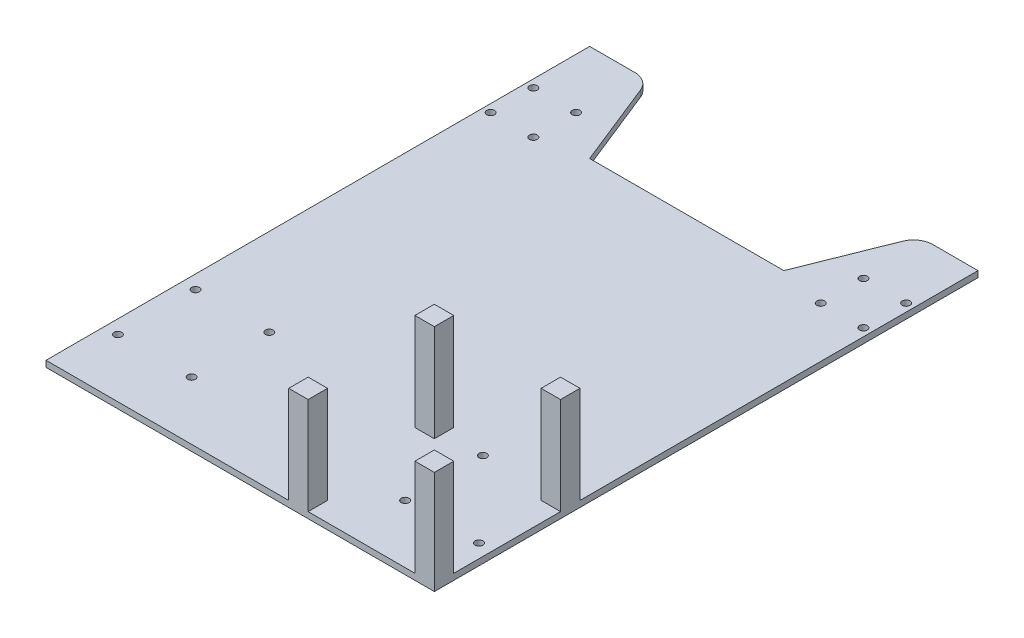
SolidWorks part; units mm, degrees
material "Pine"
ref_plane "Front Plane" through (0, 0, 0) normal (0, 0, 1) x (1, 0, 0)
ref_plane "Top Plane" through (0, 0, 0) normal (0, 1, 0) x (1, 0, 0)
ref_plane "Right Plane" through (0, 0, 0) normal (1, 0, 0) x (0, 0, -1)
sketch "Sketch3" plane through (0, 0, 0) normal (0, 1, 0) x (1, 0, 0)
  line L1 (-100, -140) -> (100, -140)
  line L2 (-100, -140) -> (-100, 140)
  line L3 (-100, 140) -> (100, 140)
  line L4 (100, -140) -> (100, 140)
  line L5 (-100, -140) -> (100, 140) construction
  line L6 (-100, 140) -> (100, -140) construction
  point P0 (0, 0)
  dimension "D1" = 200
  dimension "D2" = 280
extrude "Boss-Extrude1" add sketch "Sketch3" along normal blind 3.175
sketch "Sketch4" plane through (0, 3.175, 0) normal (0, 1, 0) x (1, 0, 0)
  line L0 (100, -140) -> (100, 140) construction
  line L1 (100, -140) -> (90, -140)
  line L2 (100, -140) -> (100, -130)
  line L3 (100, -65) -> (90, -65)
  line L4 (25, -140) -> (25, -130)
  line L5 (-100, -140) -> (100, -140) construction
  line L6 (35, -140) -> (35, -130)
  line L7 (90, -65) -> (90, -75)
  line L8 (35, -65) -> (25, -65)
  line L9 (35, -140) -> (25, -140)
  line L10 (25, -130) -> (35, -130)
  line L11 (25, -75) -> (35, -75)
  line L12 (90, -75) -> (100, -75)
  line L13 (90, -130) -> (100, -130)
  line L14 (25, -75) -> (25, -65)
  line L15 (35, -75) -> (35, -65)
  line L16 (90, -130) -> (90, -140)
  line L17 (100, -75) -> (100, -65)
  point P20 (95, -130)
  dimension "D1" = 0
  dimension "D2" = 0
  dimension "D3" = 75
  dimension "D4" = 75
  dimension "D5" = 10
  dimension "D6" = 10
  dimension "D7" = 10
  dimension "D8" = 10
  dimension "D9" = 10
extrude "Boss-Extrude2" add sketch "Sketch4" along normal blind 50
sketch "Sketch7" plane through (0, 0, 0) normal (0, -1, 0) x (1, 0, 0)
  line L0 (100, 140) -> (100, -140) construction
  line L1 (-100, 140) -> (100, 140) construction
  line L2 (100, -140) -> (-100, -140) construction
  line L3 (0, 0) -> (0, -140) construction
  line L4 (-93, 70) -> (93, 70) construction
  line L5 (-93, 110) -> (93, 110) construction
  line L6 (-100, -140) -> (-100, 140) construction
  circle A8 centre (-93, 70) radius 2
  circle A9 centre (-93, 110) radius 2
  circle A10 centre (-55, 110) radius 2
  circle A11 centre (-55, 70) radius 2
  circle A12 centre (55, 110) radius 2
  circle A13 centre (93, 110) radius 2
  circle A14 centre (93, 70) radius 2
  circle A15 centre (55, 70) radius 2
  circle A16 centre (96, -107) radius 2
  circle A17 centre (74, -85) radius 2
  circle A18 centre (96, -85) radius 2
  circle A19 centre (74, -107) radius 2
  circle A20 centre (-74, -107) radius 2
  circle A21 centre (-96, -107) radius 2
  circle A22 centre (-96, -85) radius 2
  circle A23 centre (-74, -85) radius 2
  dimension "D17" = 40
  dimension "D4" = 7
  dimension "D1" = 38
  dimension "D2" = 40
  dimension "D3" = 38
  dimension "D5" = 38
  dimension "D6" = 40
  dimension "D7" = 38
  dimension "D8" = 4
  dimension "D9" = 33
  dimension "D10" = 22
  dimension "D11" = 22
  dimension "D16" = 7
  dimension "D18" = 55.1725
  dimension "D19" = 40
  dimension "D20" = 55.1725
  dimension "D27" = 30
extrude "Cut-Extrude2" cut sketch "Sketch7" against normal blind 10
sketch "Sketch8" plane through (0, 3.175, 0) normal (0, 1, 0) x (1, 0, 0)
  line L0 (-100, -140) -> (25, -140) construction
  line L1 (-100, 140) -> (-100, -140) construction
  line L2 (100, -65) -> (100, 140) construction
  circle A0 centre (-35, -35) radius 4
  circle A1 centre (-15, -35) radius 4
  circle A5 centre (-35, 40) radius 4
  circle A6 centre (-15, 40) radius 4
  circle A7 centre (45, 2.5) radius 4
  circle A8 centre (65, 2.5) radius 4
  dimension "D1" = 8
  dimension "D2" = 8
  dimension "D4" = 8
  dimension "D5" = 8
  dimension "D7" = 8
  dimension "D8" = 8
  dimension "D3" = 20
  dimension "D6" = 20
  dimension "D9" = 20
  dimension "D10" = 105
  dimension "D11" = 65
  dimension "D12" = 65
  dimension "D13" = 75
  dimension "D14" = 37.5
  dimension "D15" = 35
extrude "Cut-Extrude3" [suppressed] cut sketch "Sketch8" against normal blind 10
sketch "Sketch9" plane through (0, 3.175, 0) normal (0, 1, 0) x (1, 0, 0)
  line L0 (100, 140) -> (-100, 140) construction
  line L1 (50, 140) -> (-50, 140)
  line L3 (50, 90) -> (-50, 90)
  line L5 (50, 98.4245) -> (100, 98.4245) construction
  line L6 (100, -65) -> (100, 140) construction
  line L7 (-50, 98.4245) -> (-100, 98.4245) construction
  line L8 (-100, 140) -> (-100, -140) construction
  line L9 (50, 140) -> (70, 140)
  line L10 (70, 140) -> (50, 90)
  line L11 (-50, 140) -> (-70, 140)
  line L12 (-70, 140) -> (-50, 90)
  dimension "D1" = 100
  dimension "D2" = 50
  dimension "D3" = 20
  dimension "D4" = 20
extrude "Cut-Extrude4" cut sketch "Sketch9" against normal blind 10
fillet "Fillet1" radius 10 2 edges at (-70, 1.5875, -140) (70, 1.5875, -140)
